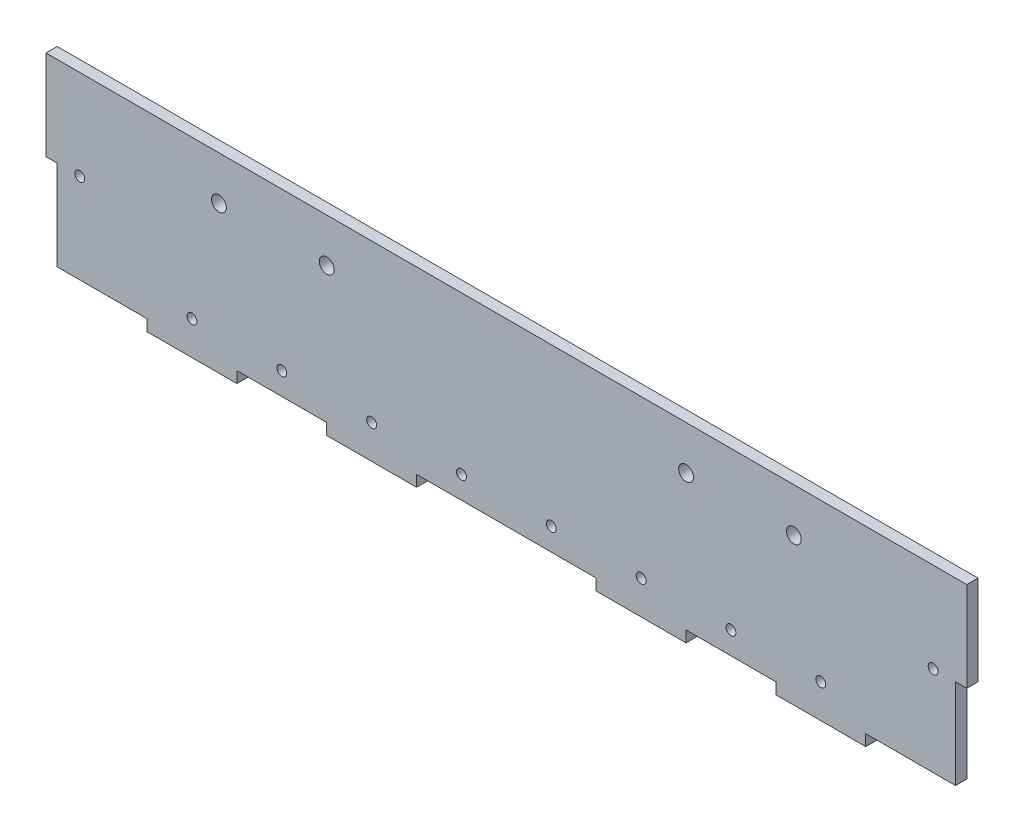
SolidWorks part; units mm, degrees
ref_plane "前视基准面" through (0, 0, 0) normal (0, 0, 1) x (1, 0, 0)
ref_plane "上视基准面" through (0, 0, 0) normal (0, 1, 0) x (1, 0, 0)
ref_plane "右视基准面" through (0, 0, 0) normal (1, 0, 0) x (0, 0, -1)
sketch "草图1" plane through (0, 0, 0) normal (0, 0, 1) x (1, 0, 0)
  line L2 (-200, 150) -> (200, 150)
  line L3 (200, -150) -> (200, -110)
  line L4 (-200, -150) -> (-200, -110)
  line L5 (-200, -150) -> (-160, -150)
  line L6 (-200, -150) -> (-160, -150)
  line L7 (-160, -150) -> (-160, -155)
  line L8 (-160, -155) -> (-120, -155)
  line L9 (-120, -155) -> (-120, -150)
  line L10 (-120, -150) -> (-80, -150)
  line L11 (-80, -150) -> (-80, -155)
  line L12 (-80, -155) -> (-40, -155)
  line L13 (-40, -155) -> (-40, -150)
  line L14 (-40, -150) -> (40, -150)
  line L15 (40, -150) -> (40, -155)
  line L16 (40, -155) -> (80, -155)
  line L17 (80, -155) -> (80, -150)
  line L18 (80, -150) -> (120, -150)
  line L19 (120, -150) -> (120, -155)
  line L20 (120, -155) -> (160, -155)
  line L21 (160, -155) -> (160, -150)
  line L22 (80, -150) -> (120, -150)
  line L23 (-120, -150) -> (-80, -150)
  line L24 (-40, -150) -> (40, -150)
  line L25 (160, -150) -> (200, -150)
  line L26 (-200, 110) -> (-200, 150)
  line L27 (-200, -70) -> (-200, -30)
  line L28 (-205, -30) -> (-205, 30)
  line L29 (-205, 30) -> (-200, 30)
  line L30 (-200, 30) -> (-200, 70)
  line L31 (-200, 70) -> (-205, 70)
  line L32 (-205, 70) -> (-205, 110)
  line L33 (-205, 110) -> (-200, 110)
  line L34 (-205, -30) -> (-200, -30)
  line L35 (-200, -70) -> (-205, -70)
  line L36 (-205, -70) -> (-205, -110)
  line L37 (-205, -110) -> (-200, -110)
  line L38 (-200, 30) -> (-200, 70)
  line L39 (200, 110) -> (200, 150)
  line L40 (205, -70) -> (205, -110)
  line L41 (205, -110) -> (200, -110)
  line L42 (200, -70) -> (205, -70)
  line L43 (205, -30) -> (200, -30)
  line L44 (205, -30) -> (205, 30)
  line L45 (205, 30) -> (200, 30)
  line L46 (200, 70) -> (205, 70)
  line L47 (205, 70) -> (205, 110)
  line L48 (205, 110) -> (200, 110)
  line L49 (200, 30) -> (200, 70)
  line L50 (200, -70) -> (200, -30)
  circle A0 centre (-140, -140) radius 2.2
  circle A1 centre (-100, -140) radius 2.2
  circle A2 centre (-60, -140) radius 2.2
  circle A3 centre (-20, -140) radius 2.2
  circle A4 centre (20, -140) radius 2.2
  circle A5 centre (60, -140) radius 2.2
  circle A6 centre (100, -140) radius 2.2
  circle A7 centre (140, -140) radius 2.2
  circle A8 centre (-190, 110) radius 2.2
  circle A9 centre (-190, 70) radius 2.2
  circle A10 centre (-190, 30) radius 2.2
  circle A11 centre (-190, -30) radius 2.2
  circle A12 centre (-190, -70) radius 2.2
  circle A13 centre (-190, -110) radius 2.2
  circle A14 centre (190, -110) radius 2.2
  circle A15 centre (190, -70) radius 2.2
  circle A16 centre (190, -30) radius 2.2
  circle A17 centre (190, 30) radius 2.2
  circle A18 centre (190, 70) radius 2.2
  circle A19 centre (190, 110) radius 2.2
extrude "凸台-拉伸1" add sketch "草图1" along normal blind 5 contours L42 L50 L43 L44 L45 L49 L46 L47 L48 L39 L2 L26 L33 L32 L31 L30 L29 L28 L34 L27 L35 L36 L37 L4 L5 L7 L8 L9 L10 L11 L12 L13 L14 L15 L16 L17 L18 L19 L20 L21 L25 L3 L41 L40 A18 A16 A14 region at (0, -0.8611, 0)
sketch "草图2" plane through (0, 0, 5) normal (0, 0, 1) x (1, 0, 0)
  line L0 (-205, -70) -> (205, -70)
  line L1 (-205, -70) -> (-205, 156.1054)
  line L2 (205, -70) -> (205, 156.1054)
  line L3 (-205, 156.1054) -> (205, 156.1054)
extrude "切除-拉伸2" cut sketch "草图2" against normal blind 5
sketch "草图4" plane through (0, 0, 5) normal (0, 0, 1) x (1, 0, 0)
  line L0 (-205, -70) -> (205, -70)
  line L1 (-205, -70) -> (-205, -89.4867)
  line L2 (205, -70) -> (205, -89.4867)
  line L3 (-205, -89.4867) -> (205, -89.4867)
extrude "凸台-拉伸3" add sketch "草图4" against normal blind 5
sketch "草图5" plane through (0, 0, 0) normal (0, 0, -1) x (-1, 0, 0)
  circle A0 centre (-80, -89.5) radius 3.3
  circle A1 centre (-128, -89.5) radius 3.3
  circle A2 centre (128, -89.5) radius 3.3
  circle A3 centre (80, -89.5) radius 3.3
extrude "切除-拉伸3" cut sketch "草图5" against normal blind 10
